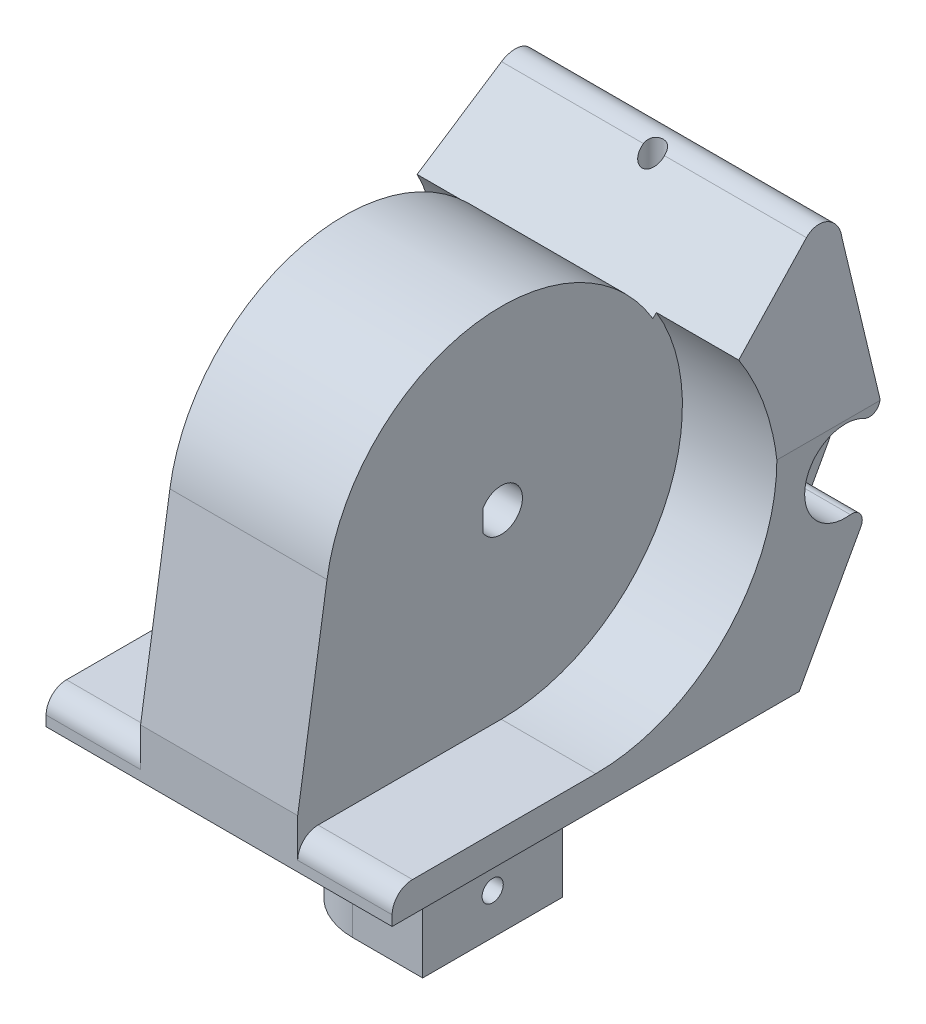
SolidWorks part; units mm, degrees
ref_plane "Front Plane" through (0, 0, 0) normal (0, 0, 1) x (1, 0, 0)
ref_plane "Top Plane" through (0, 0, 0) normal (0, 1, 0) x (1, 0, 0)
ref_plane "Right Plane" through (0, 0, 0) normal (1, 0, 0) x (0, 0, -1)
sketch "Sketch1" plane through (0, 0, 0) normal (1, 0, 0) x (0, 0, -1)
  line L0 (-27.1776, 4.1984) -> (-31.75, -25.4)
  line L1 (-31.75, -25.4) -> (-31.75, -33.02)
  line L2 (-31.75, -33.02) -> (31.75, -33.02)
  line L3 (31.75, -33.02) -> (31.75, -25.4)
  line L4 (31.75, -25.4) -> (27.1776, 4.1984)
  arc A0 (27.1776, 4.1984) -> (-27.1776, 4.1984) centre (0, 0) ccw
  arc A1 (-27.1776, 4.1984) -> (27.1776, 4.1984) centre (0, 0) ccw construction
  point P10 (0, -33.02)
  dimension "D1" = 55
  dimension "D2" = 63.5
  dimension "D3" = 33.02
  dimension "D4" = 25.4
extrude "Boss-Extrude1" add sketch "Sketch1" along normal mid plane 53.975
sketch "Sketch2" plane through (0, 0, 0) normal (1, 0, 0) x (0, 0, -1)
  line L0 (23.6274, 14.0712) -> (36.0802, 24.5203)
  line L1 (0, 0) -> (27.8262, 0) construction
  line L2 (6.858, 0) -> (23.6274, 14.0712) construction
  line L3 (36.0802, 24.5203) -> (40.4401, 28.1787) construction
  line L4 (40.4401, 28.1787) -> (41.296, 22.0881) construction
  line L5 (41.296, 22.0881) -> (45.2349, -5.9382)
  line L6 (-27.1776, 4.1984) -> (-31.75, -25.4)
  line L7 (-31.75, -25.4) -> (-31.75, -33.02)
  line L8 (-31.75, -33.02) -> (31.75, -33.02)
  line L9 (31.75, -33.02) -> (31.75, -25.4)
  line L10 (31.75, -25.4) -> (27.1776, 4.1984)
  line L11 (-27.1776, 4.1984) -> (-31.75, -25.4) construction
  line L12 (-31.75, -25.4) -> (-31.75, -33.02) construction
  line L13 (-31.75, -33.02) -> (31.75, -33.02) construction
  line L14 (31.75, -33.02) -> (31.75, -25.4)
  line L15 (31.75, -25.4) -> (27.1776, 4.1984)
  line L16 (31.75, -33.02) -> (44.5071, -9.8886)
  arc A0 (41.296, 22.0881) -> (36.0802, 24.5203) centre (38.121, 22.0881) ccw
  arc A1 (27.1776, 4.1984) -> (-27.1776, 4.1984) centre (0, 0) ccw
  arc A2 (27.1776, 4.1984) -> (23.6274, 14.0712) centre (0, 0) ccw
  arc A3 (44.5071, -9.8886) -> (45.2349, -5.9382) centre (38.9467, -6.822) ccw
  arc A4 (45.2349, -5.9382) -> (44.5071, -9.8886) centre (38.9467, -6.822) ccw construction
  arc A5 (23.6274, 14.0712) -> (-27.1776, 4.1984) centre (0, 0) ccw construction
  arc A6 (36.0802, 24.5203) -> (41.296, 22.0881) centre (38.121, 22.0881) ccw construction
  circle A7 centre (38.9467, -6.822) radius 3.175
  dimension "D4" = 6.35
  dimension "D8" = 12.7
  dimension "D10" = 6.35
  dimension "D1" = 6.858
  dimension "D3" = 40
  dimension "D5" = 16.256
  dimension "D6" = 58
  dimension "D7" = 5.6914
  dimension "D9" = 26.416
  dimension "D2" = 0
extrude "Boss-Extrude2" add sketch "Sketch2" along normal mid plane 53.975
sketch "Sketch3" plane through (26.9875, 0, 0) normal (1, 0, 0) x (0, 0, -1)
  line L0 (0, -28.262) -> (-28.575, -28.262)
  line L1 (-31.75, -25.4) -> (-31.75, -33.02) construction
  line L2 (36.0802, 24.5203) -> (23.6274, 14.0712) construction
  line L3 (36.0802, 24.5203) -> (23.6274, 14.0712) construction
  line L4 (-27.1776, 4.1984) -> (-31.75, -25.4) construction
  line L5 (-27.1776, 4.1984) -> (-31.75, -25.4)
  line L6 (-31.75, -25.4) -> (-31.75, -33.02) construction
  line L7 (23.6274, 14.0712) -> (24.2185, 14.5672)
  line L8 (-31.75, -25.4) -> (-31.75, -31.437)
  arc A0 (23.6274, 14.0712) -> (-27.1776, 4.1984) centre (0, 0) ccw construction
  arc A1 (23.6274, 14.0712) -> (-27.1776, 4.1984) centre (0, 0) ccw construction
  arc A2 (0, -28.262) -> (24.2185, 14.5672) centre (0, 0) ccw
  arc A3 (23.6274, 14.0712) -> (-27.1776, 4.1984) centre (0, 0) ccw
  arc A4 (-28.575, -28.262) -> (-31.75, -31.437) centre (-28.575, -31.437) ccw
  arc A5 (-28.1728, -2.2437) -> (0, -28.262) centre (0, 0) ccw construction
  arc A6 (-27.1776, 4.1984) -> (23.6274, 14.0712) centre (0, 0) ccw construction
  arc A7 (24.2185, 14.5672) -> (-28.1728, -2.2437) centre (0, 0) ccw construction
  arc A8 (-31.75, -31.437) -> (-28.575, -28.262) centre (-28.575, -31.437) ccw construction
  dimension "D1" = 0.762
  dimension "D2" = 6.35
extrude "Cut-Extrude1" cut sketch "Sketch3" against normal blind 14.732
mirror "Mirror1" about plane through (0, 0, 0) normal (1, 0, 0) of "Cut-Extrude1"
sketch "Sketch4" plane through (0, -33.02, 0) normal (0, -1, 0) x (1, 0, 0)
  line L0 (0, 10.922) -> (10.922, 10.922)
  line L1 (10.922, 10.922) -> (10.922, -10.922)
  line L2 (10.922, -10.922) -> (0, -10.922)
  arc A0 (0, 10.922) -> (0, -10.922) centre (0, 0) ccw
  arc A1 (0, -10.922) -> (10.922, 0) centre (0, 0) ccw construction
  arc A2 (10.922, 0) -> (0, 10.922) centre (0, 0) ccw construction
  dimension "D1" = 21.844
extrude "Boss-Extrude3" add sketch "Sketch4" along normal blind 25.4
sketch "Sketch5" plane through (0, -58.42, 0) normal (0, -1, 0) x (1, 0, 0)
  line L0 (0, -7.62) -> (7.62, -7.62)
  line L1 (7.62, -7.62) -> (7.62, 7.62)
  line L2 (7.62, 7.62) -> (0, 7.62)
  line L3 (0, -10.922) -> (10.922, -10.922)
  line L4 (10.922, -10.922) -> (10.922, 10.922)
  line L5 (10.922, 10.922) -> (0, 10.922)
  line L6 (0, -10.922) -> (10.922, -10.922) construction
  line L7 (10.922, -10.922) -> (10.922, 10.922) construction
  line L8 (10.922, 10.922) -> (0, 10.922) construction
  arc A0 (0, 7.62) -> (0, -7.62) centre (0, 0) ccw
  arc A1 (0, 10.922) -> (0, -10.922) centre (0, 0) ccw
  arc A2 (0, 10.922) -> (0, -10.922) centre (0, 0) ccw construction
  dimension "D1" = 0
  dimension "D2" = 3.302
extrude "Cut-Extrude2" cut sketch "Sketch5" against normal up to surface (25.4 mm away) up to face at (0, -33.02, 0)
sketch "Sketch6" plane through (0, 0, 0) normal (0, 0, 1) x (1, 0, 0)
  line L0 (-26.9875, 14.5672) -> (-26.9875, -28.262) construction
  line L1 (-26.9875, 24.5203) -> (-26.9875, 14.5672) construction
  line L2 (26.9875, 25.2631) -> (-26.9875, 25.2631) construction
  line L3 (26.9875, -28.262) -> (26.9875, 14.5672) construction
  line L4 (26.9875, 24.5203) -> (26.9875, 14.5672) construction
  line L5 (-26.9875, 14.5672) -> (-26.9875, -28.262) construction
  line L6 (-26.9875, 24.5203) -> (-26.9875, 14.5672) construction
  line L7 (26.9875, 25.2631) -> (-26.9875, 25.2631) construction
  line L8 (26.9875, -28.262) -> (26.9875, 14.5672) construction
  line L9 (26.9875, 24.5203) -> (26.9875, 14.5672) construction
  line L10 (23.6855, 25.2631) -> (26.9875, 25.2631)
  line L11 (0, 0) -> (26.9875, 0) construction
  line L12 (26.9875, 25.2631) -> (26.9875, 0)
  line L13 (23.6855, 25.2631) -> (26.9875, 0)
  line L14 (0, -33.286) -> (0, 33.286) construction
  line L15 (-23.6855, 25.2631) -> (-26.9875, 25.2631)
  line L16 (-26.9875, 25.2631) -> (-26.9875, 0)
  line L17 (-23.6855, 25.2631) -> (-26.9875, 0)
  dimension "D1" = 3.302
extrude "Cut-Extrude3" cut sketch "Sketch6" against normal through all both and the other way through all contours L13 L12 L10 | L15 L16 L17
sketch "Sketch7" plane through (26.9875, 0, 0) normal (1, 0, 0) x (0, 0, -1)
  line L0 (31.75, -33.02) -> (44.5071, -9.8886) construction
  line L1 (45.2349, -5.9382) -> (44.4003, 0) construction
  line L2 (45.2349, -5.9382) -> (44.4003, 0)
  line L3 (41.3798, -15.5592) -> (44.5071, -9.8886)
  line L4 (41.296, 22.0881) -> (44.4003, 0) construction
  line L5 (44.3336, 0.4745) -> (44.4003, 0)
  line L6 (31.75, -33.02) -> (41.3798, -15.5592) construction
  line L7 (41.296, 22.0881) -> (44.3336, 0.4745) construction
  circle A0 centre (38.9467, -6.822) radius 3.175 construction
  circle A1 centre (38.9467, -6.822) radius 3.175 construction
  arc A2 (44.5071, -9.8886) -> (45.2349, -5.9382) centre (38.9467, -6.822) ccw
  arc A3 (41.3798, -15.5592) -> (39.7303, -13.1235) centre (39.9341, -14.7618) ccw
  arc A4 (44.5071, -9.8886) -> (45.2349, -5.9382) centre (38.9467, -6.822) ccw construction
  arc A5 (44.5071, -9.8886) -> (45.2349, -5.9382) centre (38.9467, -6.822) ccw construction
  arc A6 (41.9245, -1.2135) -> (44.3336, 0.4745) centre (42.6987, 0.2447) ccw
  arc A7 (39.7303, -13.1235) -> (44.5071, -9.8886) centre (38.9467, -6.822) ccw construction
  arc A8 (45.2349, -5.9382) -> (41.9245, -1.2135) centre (38.9467, -6.822) ccw construction
  arc A9 (41.9245, -1.2135) -> (39.7303, -13.1235) centre (38.9467, -6.822) ccw
  arc A10 (39.7303, -13.1235) -> (41.3798, -15.5592) centre (39.9341, -14.7618) ccw construction
  arc A11 (44.3336, 0.4745) -> (41.9245, -1.2135) centre (42.6987, 0.2447) ccw construction
  dimension "D1" = 3.302
extrude "Cut-Extrude4" cut sketch "Sketch7" against normal blind 8.255
mirror "Mirror2" about plane through (0, 0, 0) normal (1, 0, 0) of "Cut-Extrude4"
ref_plane "Plane1" through (0, 0, -32.7018) normal (0, 0, 1) x (1, 0, 0)
sketch "Sketch8" plane through (0, 0, -32.7018) normal (0, 0, 1) x (1, 0, 0)
  line L0 (26.9875, -33.02) -> (-26.9875, -33.02) construction
  line L1 (26.9875, -33.02) -> (-26.9875, -33.02) construction
  line L2 (-18.796, -33.02) -> (18.796, -33.02)
  line L3 (18.796, -33.02) -> (18.796, -29.718)
  line L4 (18.796, -29.718) -> (12.7031, -15.1964)
  line L5 (12.446, -0.4569) -> (12.446, -13.9189)
  line L6 (-18.796, -33.02) -> (-18.796, -29.718)
  line L7 (-18.796, -29.718) -> (-12.7031, -15.1964)
  line L8 (-12.446, -0.4569) -> (-12.446, -13.9189)
  line L9 (12.446, -0.4569) -> (-12.446, -0.4569)
  arc A0 (12.446, -13.9189) -> (12.7031, -15.1964) centre (15.748, -13.9189) ccw
  arc A1 (-12.7031, -15.1964) -> (-12.446, -13.9189) centre (-15.748, -13.9189) ccw
  arc A2 (12.7031, -15.1964) -> (12.446, -13.9189) centre (15.748, -13.9189) ccw construction
  arc A3 (-12.446, -13.9189) -> (-12.7031, -15.1964) centre (-15.748, -13.9189) ccw construction
  point P5 (0, -33.02)
  dimension "D2" = 6.604
  dimension "D5" = 15.748
  dimension "D1" = 37.592
  dimension "D3" = 13.462
  dimension "D4" = 24.892
  dimension "D6" = 3.302
extrude "Cut-Extrude5" cut sketch "Sketch8" against normal up to next
sketch "Sketch9" plane through (0, 0, 0) normal (1, 0, 0) x (0, 0, -1)
  line L0 (44.3336, 0.4745) -> (32.5967, 0.4745)
  line L1 (32.5967, -6.822) -> (32.5967, 0.4745)
  arc A1 (41.9245, -1.2135) -> (39.7303, -13.1235) centre (38.9467, -6.822) ccw construction
  arc A2 (41.9245, -1.2135) -> (44.3336, 0.4745) centre (42.6987, 0.2447) ccw construction
  arc A3 (41.9245, -1.2135) -> (32.5967, -6.822) centre (38.9467, -6.822) ccw
  arc A4 (41.9245, -1.2135) -> (44.3336, 0.4745) centre (42.6987, 0.2447) ccw
  point P7 (32.6542, 0.4745)
extrude "Boss-Extrude4" add sketch "Sketch9" along normal up to surface and the other way up to surface up to face at (12.446, -3.647, -38.9467) other way up to face at (-12.446, -9.997, -38.9467)
sketch "Sketch11" plane through (0, 0, 0) normal (0, 1, 0) x (1, 0, 0)
  line L0 (0, 0) -> (0, 35.8768) construction
  line L2 (12.446, 32.7018) -> (-12.446, 32.7018) construction
  line L3 (12.446, 32.7018) -> (-12.446, 32.7018) construction
  circle A0 centre (0, 35.8768) radius 3.175
  point P4 (0, 30.1714)
  point P7 (0, 29.5268)
  point P8 (0, 37.2258)
  dimension "D1" = 6.35
extrude "Cut-Extrude6" cut sketch "Sketch11" against normal up to vertex (5.6715 mm away) up to point (12.446, -5.6715, -32.7018)
sketch "Sketch12" plane through (0, 0, 0) normal (0, 1, 0) x (1, 0, 0)
  circle A0 centre (0, 35.8768) radius 1.651
  circle A1 centre (0, 35.8768) radius 3.175 construction
  circle A2 centre (0, 35.8768) radius 3.175 construction
  dimension "D1" = 3.302
extrude "Cut-Extrude7" cut sketch "Sketch12" along normal up to next
sketch "Sketch13" plane through (-12.2555, 0, 0) normal (-1, 0, 0) x (0, 0, 1)
  line L0 (2.8596, 1.651) -> (2.8596, -1.651)
  arc A0 (2.8596, 1.651) -> (2.8596, -1.651) centre (0, 0) ccw
  arc A1 (2.8596, -1.651) -> (2.8596, 1.651) centre (0, 0) ccw construction
  dimension "D1" = 6.604
  dimension "D2" = 3.302
extrude "Cut-Extrude8" cut sketch "Sketch13" against normal through all and the other way through all
sketch "Sketch14" plane through (10.922, 0, 0) normal (1, 0, 0) x (0, 0, -1)
  line L0 (10.922, -58.42) -> (-10.922, -58.42) construction
  line L1 (10.922, -33.02) -> (-10.922, -33.02) construction
  line L2 (10.922, -58.42) -> (-10.922, -58.42) construction
  line L3 (10.922, -33.02) -> (-10.922, -33.02) construction
  line L4 (0, -33.02) -> (0, -58.42) construction
  circle A0 centre (0, -39.37) radius 1.651
  circle A1 centre (0, -52.07) radius 1.651
  point P10 (0, -53.526)
  dimension "D1" = 3.302
  dimension "D2" = 6.35
  dimension "D3" = 6.35
extrude "Cut-Extrude9" cut sketch "Sketch14" against normal through all
